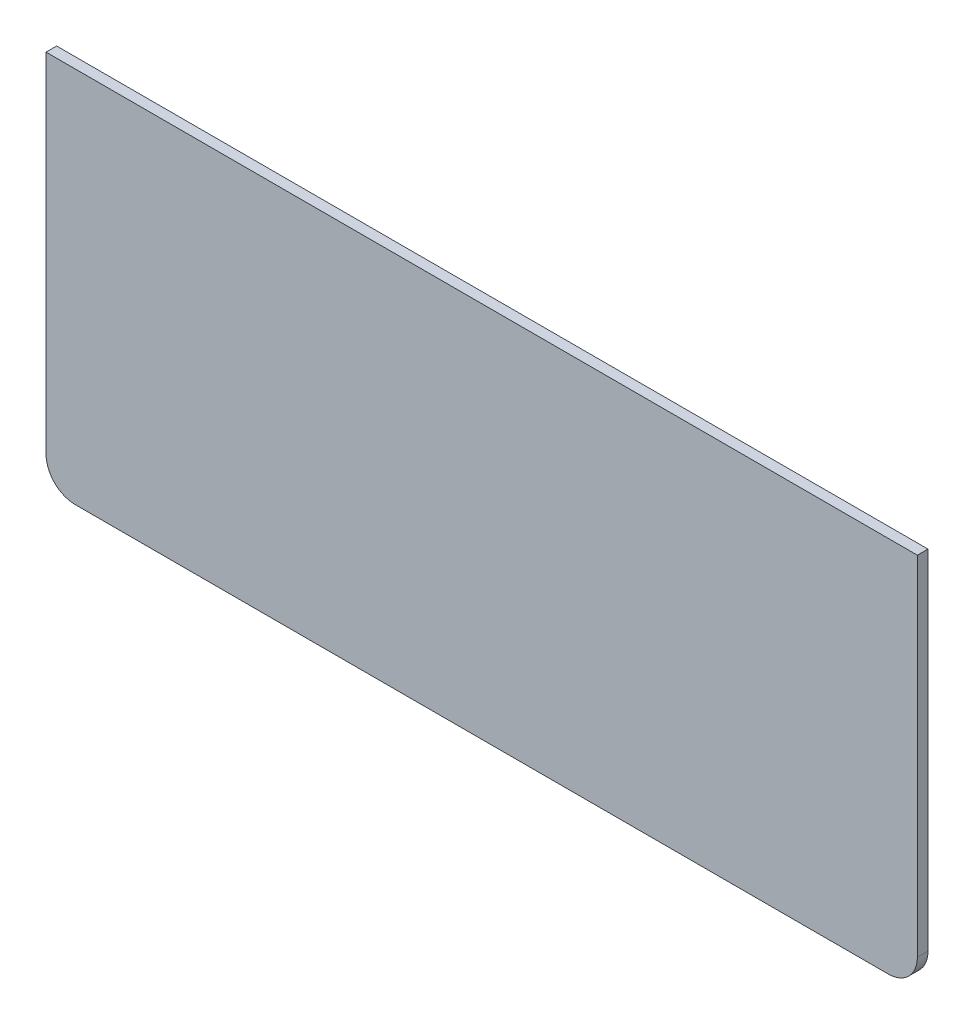
SolidWorks part; units mm, degrees
material "5052-H32"
ref_plane "Front Plane" through (0, 0, 0) normal (0, 0, 1) x (1, 0, 0)
ref_plane "Top Plane" through (0, 0, 0) normal (0, 1, 0) x (1, 0, 0)
ref_plane "Right Plane" through (0, 0, 0) normal (1, 0, 0) x (0, 0, -1)
sketch "Sketch2" plane through (0, 0, 0) normal (0, 0, 1) x (1, 0, 0)
  line L0 (-53.5866, 40.5355) -> (207.7634, 40.5355)
  line L1 (207.7634, 40.5355) -> (207.7634, -72.6395)
  line L2 (207.7634, -72.6395) -> (-53.5866, -72.6395)
  line L3 (-53.5866, -72.6395) -> (-53.5866, 40.5355)
  dimension "D1" = 113.175
  dimension "D2" = 261.35
extrude "Boss-Extrude1" add sketch "Sketch2" along normal blind 3.175
fillet "Fillet1" radius 8.7312 2 edges at (-53.5866, -72.6395, 1.5875) (207.7634, -72.6395, 1.5875)
equation "\"L\"= 385"
equation "\"W\"= 255"
equation "\"H\"= 110"
equation "\"Compartment Width\"= 80"
equation "\"T\"= 4.7625 * 2 / 3"
equation "\"Inside Fillet Radius\"= 5.55625"
equation "\"D1@Fillet1\"=\"Inside Fillet Radius\"+\"T\""
equation "\"D1@Sketch2\"=\"T\"+\"H\""
equation "\"D2@Sketch2\"=2*\"T\"+\"W\""
equation "\"D1@Boss-Extrude1\"=\"T\""
equation "\"Offset\"= 30"
equation "\"Hole\"=15"
equation "\"Wheel to Wall\"= 50"
